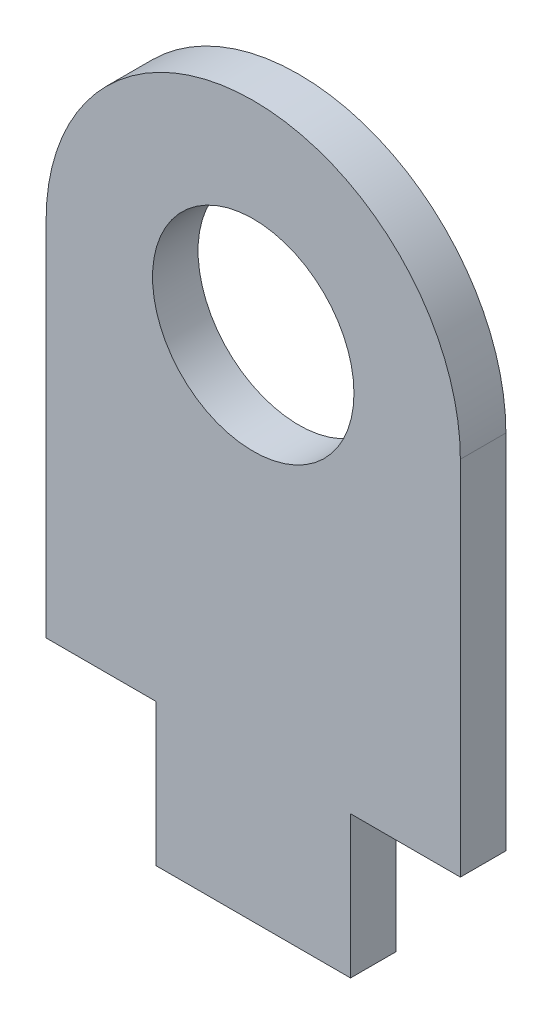
SolidWorks part; units mm, degrees
material "Brass"
ref_plane "Front Plane" through (0, 0, 0) normal (0, 0, 1) x (1, 0, 0)
ref_plane "Top Plane" through (0, 0, 0) normal (0, 1, 0) x (1, 0, 0)
ref_plane "Right Plane" through (0, 0, 0) normal (1, 0, 0) x (0, 0, -1)
sketch "Sketch1" plane through (0, 0, 0) normal (0, 0, 1) x (1, 0, 0)
  line L0 (-4.6228, 6.35) -> (4.6228, 6.35)
  line L5 (4.6228, 6.35) -> (4.6228, -6.35)
  line L6 (4.6228, -6.35) -> (2.1717, -6.35)
  line L7 (2.1717, -6.35) -> (2.1717, -9.525)
  line L8 (2.1717, -9.525) -> (-2.1717, -9.525)
  line L9 (-2.1717, -9.525) -> (-2.1717, -6.35)
  line L10 (-2.1717, -6.35) -> (-4.6228, -6.35)
  line L11 (-4.6228, -6.35) -> (-4.6228, 6.35)
  point P2 (4.6228, 0)
  point P10 (0, 6.35)
  dimension "D1" = 12.7
  dimension "D2" = 3.175
  dimension "D3" = 4.3434
  dimension "D4" = 9.2456
extrude "Boss-Extrude1" add sketch "Sketch1" along normal mid plane 1.016
sketch "Sketch2" plane through (0, 0, 0.508) normal (0, 0, 1) x (1, 0, 0)
  line L0 (4.6228, 6.35) -> (-4.6228, 6.35) construction
  circle A0 centre (0, 1.8161) radius 2.2479
  dimension "D2" = 4.4958
  dimension "D1" = 2.286
extrude "Cut-Extrude1" cut sketch "Sketch2" against normal through all
fillet "Fillet1" 2 edges at (4.6228, 6.35, 0) (-4.6228, 6.35, 0) type full round first side face at (4.6228, 0, 0) second side face at (-4.6228, 0, 0) middle face at (0, 6.35, 0)
